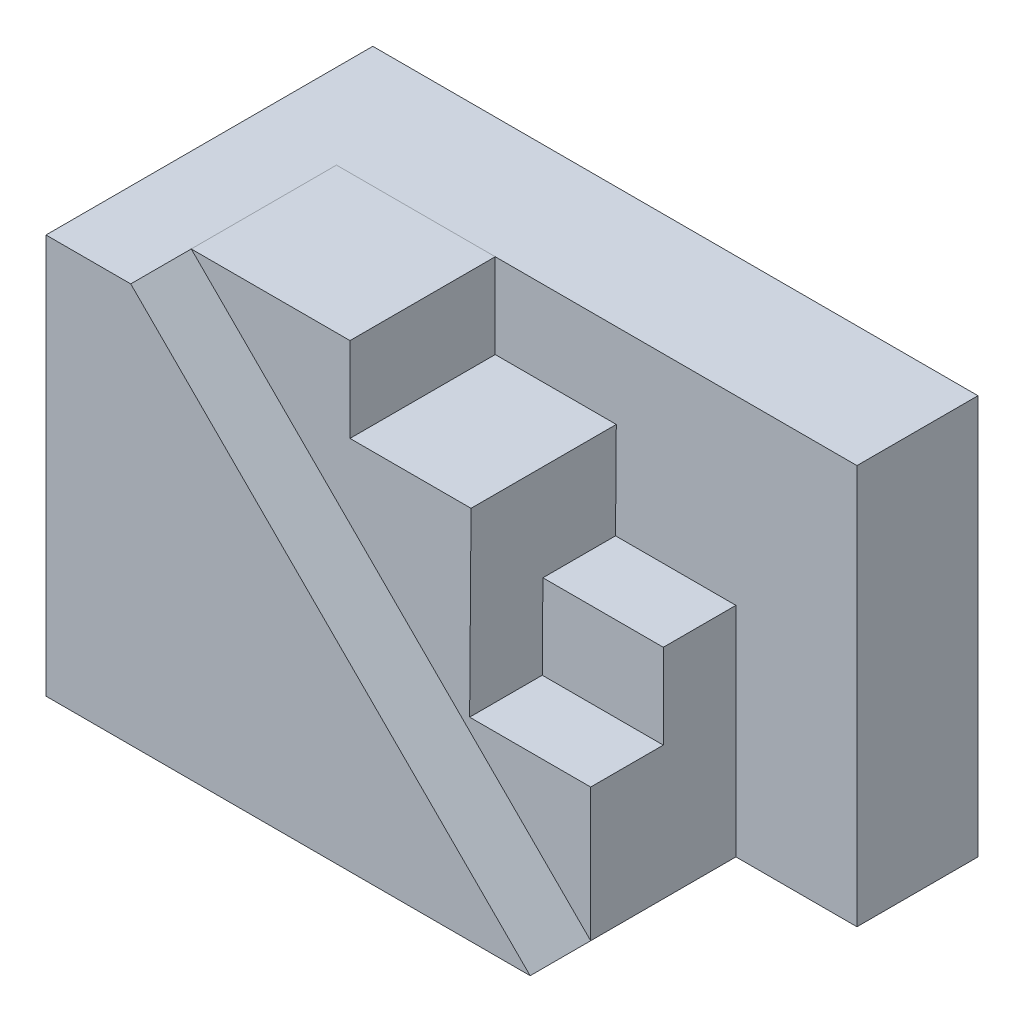
SolidWorks part; units mm, degrees
ref_plane "前基準面" through (0, 0, 0) normal (0, 0, 1) x (1, 0, 0)
ref_plane "上基準面" through (0, 0, 0) normal (0, 1, 0) x (1, 0, 0)
ref_plane "右基準面" through (0, 0, 0) normal (1, 0, 0) x (0, 0, -1)
sketch "草圖2" plane through (0, 0, 0) normal (0, 0, 1) x (1, 0, 0)
  line L0 (-12.2044, 15.8436) -> (20.7956, -17.1564)
  line L1 (-19.2044, 15.8436) -> (-12.2044, 15.8436)
  line L2 (-19.2044, 15.8436) -> (-19.2044, -17.1564)
  line L3 (-19.2044, -17.1564) -> (20.7956, -17.1564)
  line L4 (20.7956, -17.1564) -> (30.7956, -17.1564)
  line L5 (-19.2044, 15.8436) -> (20.7956, -17.1564) construction
  line L6 (-19.2044, -17.1564) -> (1.9221, 1.7171) construction
  line L7 (30.7956, -17.1564) -> (30.7956, 15.8481)
  line L8 (-12.2044, 15.8436) -> (30.7956, 15.8481)
  line L9 (0.9112, 8.845) -> (0.9112, 15.845)
  line L12 (0.9112, 8.845) -> (10.9112, 8.845)
  line L13 (20.7956, -17.1564) -> (20.7956, -6.1564)
  line L14 (20.7956, -6.1564) -> (10.7956, -6.1564)
  line L15 (10.9112, 8.845) -> (10.7956, -6.1564)
  line L16 (20.7956, -6.1564) -> (20.7956, 0.8436)
  line L17 (20.7956, 0.8436) -> (10.8534, 1.3443)
  point P0 (0, 0)
  dimension "D1" = 40
  dimension "D2" = 7
  dimension "D3" = 33
  dimension "D4" = 10
  dimension "D5" = 7
  dimension "D7" = 10
  dimension "D8" = 11
  dimension "D9" = 10
  dimension "D10" = 7
extrude "填料-伸長1" add sketch "草圖2" along normal blind 17 contours L2 L3 L0 L1 region at (-5.5235, -4.5181, 0)
extrude "填料-伸長2" add sketch "草圖2<3>" along normal blind 12 contours L15 L12 L8 L0 L13 L14 region at (5.7109, 2.8153, 0)
sketch "草圖2<3>" plane through (0, 0, 0) normal (0, 0, 1) x (1, 0, 0) same geometry as "草圖2"
sketch "草圖3" plane through (20.7956, 0, 0) normal (1, 0, 0) x (0, 0, -1)
  line L0 (-12, -6.1564) -> (0, -6.1564) construction
  line L1 (-6, -6.1564) -> (0, -6.1564)
  line L2 (-6, -6.1564) -> (-6, 0.8436)
  line L3 (-6, 0.8436) -> (0, 0.8436)
  line L4 (0, -6.1564) -> (0, 0.8436)
  dimension "D1" = 7
  dimension "D2" = 6
extrude "填料-伸長3" add sketch "草圖3" against normal blind 12
sketch "草圖4" plane through (20.7956, 0, 0) normal (1, 0, 0) x (0, 0, -1)
  line L1 (0, -17.1564) -> (10, -17.1564)
  line L2 (0, -17.1564) -> (0, 15.8436)
  line L3 (0, 15.8436) -> (10, 15.8436)
  line L4 (10, -17.1564) -> (10, 15.8436)
  dimension "D1" = 10
  dimension "D2" = 33
extrude "填料-伸長4" add sketch "草圖4" against normal up to surface (40 mm away) separate body up to face at (-19.2044, -0.6564, 8.5)
sketch "草圖6" plane through (20.7956, 0, 0) normal (1, 0, 0) x (0, 0, -1)
  line L0 (5, 15.8436) -> (10, 10.8436)
  line L1 (10, 15.8436) -> (0, 15.8436) construction
  line L2 (10, -17.1564) -> (10, 15.8436) construction
  line L3 (5, 15.8436) -> (10, 15.8436)
  line L4 (10, 15.8436) -> (10, 10.8436)
  dimension "D1" = 5
  dimension "D2" = 5
sketch "草圖7" plane through (0, 15.8436, 0) normal (0, 1, 0) x (1, 0, 0)
  line L0 (15.7956, 10) -> (20.7956, 5)
  line L1 (-19.2044, 10) -> (20.7956, 10) construction
  line L2 (20.7956, 10) -> (20.7956, 0) construction
  line L3 (20.7956, 5) -> (20.7956, 10)
  line L4 (20.7956, 10) -> (15.7956, 10)
  line L5 (15.7956, 10) -> (15.7956, 10.0825)
  dimension "D1" = 5
  dimension "D2" = 5
sketch "草圖8" plane through (0, 0, -10) normal (0, 0, -1) x (-1, 0, 0)
  line L0 (-20.7956, 10.8436) -> (-15.7956, 15.8436)
  line L1 (-20.7956, -17.1564) -> (-20.7956, 15.8436) construction
  line L2 (19.2044, 15.8436) -> (-20.7956, 15.8436) construction
  line L3 (-15.7956, 15.8436) -> (-20.7956, 15.8436)
  line L4 (-20.7956, 15.8436) -> (-20.7956, 10.8436) construction
  line L5 (-15.7956, 15.8436) -> (-20.7956, 15.8436) construction
  line L6 (-20.7956, 15.8436) -> (-20.7956, 10.8436)
  dimension "D1" = 5
  dimension "D2" = 5
sketch "草圖10" plane through (20.7956, 0, 0) normal (1, 0, 0) x (0, 0, -1)
  line L1 (0, 15.8436) -> (10, 15.8436)
  line L2 (0, 15.8436) -> (0, -17.1564)
  line L3 (0, -17.1564) -> (10, -17.1564)
  line L4 (10, 15.8436) -> (10, -17.1564)
extrude "填料-伸長5" add sketch "草圖10" along normal blind 10
